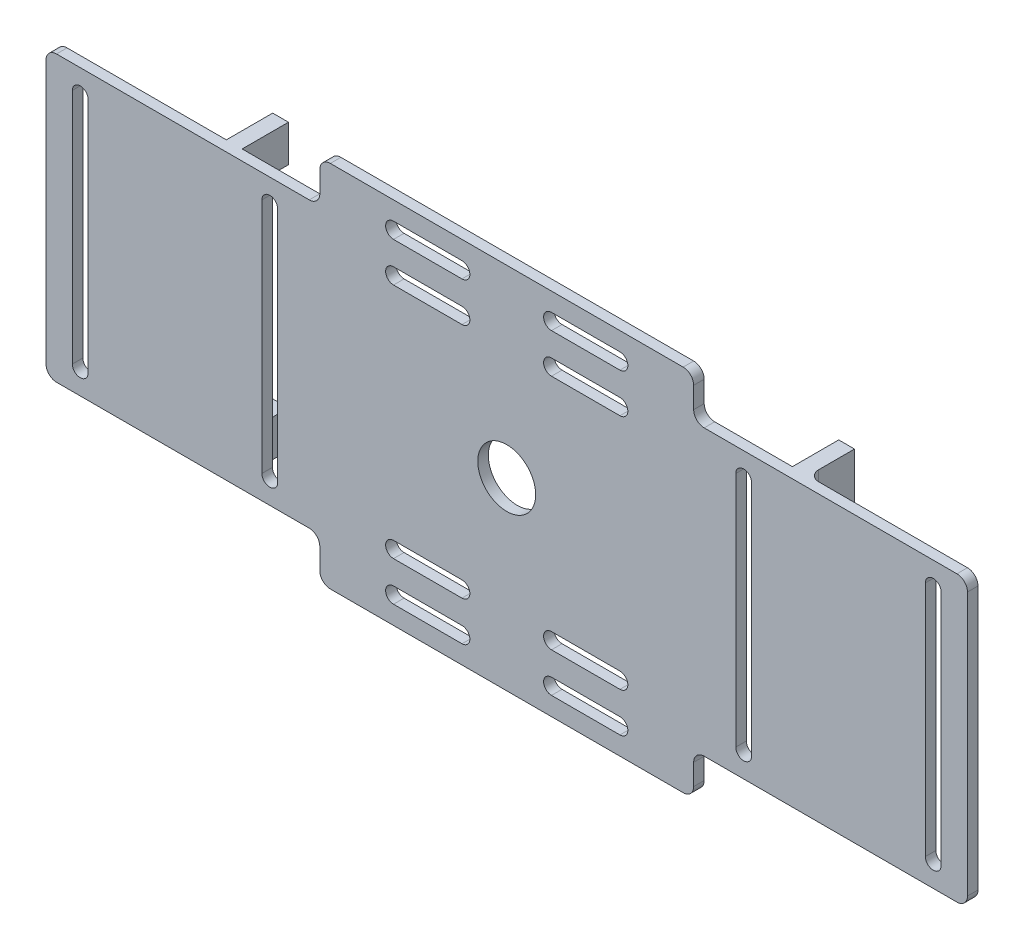
SolidWorks part; units mm, degrees
ref_plane "前基準面" through (0, 0, 0) normal (0, 0, 1) x (1, 0, 0)
ref_plane "上基準面" through (0, 0, 0) normal (0, 1, 0) x (1, 0, 0)
ref_plane "右基準面" through (0, 0, 0) normal (1, 0, 0) x (0, 0, -1)
sketch "草圖1" plane through (0, 0, 0) normal (0, 0, 1) x (1, 0, 0)
  line L0 (35.5, 33) -> (35.5, 29)
  line L1 (-33.5, 35) -> (33.5, 35)
  line L2 (-87.5, 25) -> (-87.5, -25)
  line L3 (-33.5, -35) -> (33.5, -35)
  line L4 (87.5, 25) -> (87.5, -25)
  line L5 (-85, 35) -> (85, -35) construction
  line L6 (-85, -35) -> (85, 35) construction
  line L7 (37.5, 27) -> (85.5, 27)
  line L8 (0, 72.342) -> (0, -45.5052) construction
  line L9 (-37.5, 27) -> (-85.5, 27)
  line L10 (124.9211, 0) -> (-91.026, 0) construction
  line L11 (-35.5, 33) -> (-35.5, 29)
  line L12 (37.5, -27) -> (85.5, -27)
  line L13 (35.5, -33) -> (35.5, -29)
  line L14 (-35.5, -33) -> (-35.5, -29)
  line L15 (-37.5, -27) -> (-85.5, -27)
  arc A0 (35.5, 33) -> (33.5, 35) centre (33.5, 33) ccw
  arc A1 (37.5, 27) -> (35.5, 29) centre (37.5, 29) cw
  arc A2 (87.5, 25) -> (85.5, 27) centre (85.5, 25) ccw
  arc A3 (-87.5, 25) -> (-85.5, 27) centre (-85.5, 25) cw
  arc A4 (-37.5, 27) -> (-35.5, 29) centre (-37.5, 29) ccw
  arc A5 (-35.5, 33) -> (-33.5, 35) centre (-33.5, 33) cw
  arc A6 (87.5, -25) -> (85.5, -27) centre (85.5, -25) cw
  arc A7 (37.5, -27) -> (35.5, -29) centre (37.5, -29) ccw
  arc A8 (35.5, -33) -> (33.5, -35) centre (33.5, -33) cw
  arc A9 (-35.5, -33) -> (-33.5, -35) centre (-33.5, -33) ccw
  arc A10 (-37.5, -27) -> (-35.5, -29) centre (-37.5, -29) cw
  arc A11 (-87.5, -25) -> (-85.5, -27) centre (-85.5, -25) ccw
  point P0 (0, 0)
  point P13 (35.5, 27)
  point P29 (-35.5, 27)
  point P39 (35.5, -27)
  point P49 (-35.5, -27)
  dimension "D1" = 2
  dimension "D2" = 2
  dimension "D3" = 2
  dimension "D4" = 175
  dimension "D5" = 70
  dimension "D6" = 52
  dimension "D7" = 8
extrude "填料-伸長1" add sketch "草圖1" along normal blind 2
sketch "草圖2" plane through (0, 0, 2) normal (0, 0, 1) x (1, 0, 0)
  line L0 (-1000, 0) -> (49000, 0) construction
  line L1 (45, -986.1952) -> (45, 49013.8048) construction
  line L2 (-81, -962.7943) -> (-81, 49037.2057) construction
  line L3 (45, -22.5) -> (45, 22.5) construction
  line L4 (43.5, -22.5) -> (43.5, 22.5)
  line L5 (46.5, -22.5) -> (46.5, 22.5)
  line L6 (-45, -1000) -> (-45, 49000) construction
  line L7 (-45, -22.5) -> (-45, 22.5) construction
  line L8 (-46.5, -22.5) -> (-46.5, 22.5)
  line L9 (-43.5, -22.5) -> (-43.5, 22.5)
  line L10 (0, -1000) -> (0, 49000) construction
  line L11 (-1005.6924, 30) -> (48994.3076, 30) construction
  line L12 (-1002.3566, -30) -> (48997.6434, -30) construction
  line L13 (21.5, 30) -> (8.5, 30) construction
  line L16 (21.5, 28.5) -> (8.5, 28.5)
  line L19 (81, -968.4295) -> (81, 49031.5705) construction
  line L20 (-81, -22.5) -> (-81, 22.5) construction
  line L21 (-82.5, -22.5) -> (-82.5, 22.5)
  line L22 (-79.5, -22.5) -> (-79.5, 22.5)
  line L23 (81, -22.5) -> (81, 22.5) construction
  line L24 (79.5, -22.5) -> (79.5, 22.5)
  line L25 (82.5, -22.5) -> (82.5, 22.5)
  line L26 (21.5, 31.5) -> (8.5, 31.5)
  line L27 (21.5, 22.5) -> (8.5, 22.5) construction
  line L28 (21.5, 21) -> (8.5, 21)
  line L29 (21.5, 24) -> (8.5, 24)
  line L30 (-21.5, 30) -> (-8.5, 30) construction
  line L31 (-21.5, 28.5) -> (-8.5, 28.5)
  line L32 (-21.5, 31.5) -> (-8.5, 31.5)
  line L33 (-21.5, 22.5) -> (-8.5, 22.5) construction
  line L34 (-21.5, 21) -> (-8.5, 21)
  line L35 (-21.5, 24) -> (-8.5, 24)
  line L36 (21.5, -30) -> (8.5, -30) construction
  line L37 (21.5, -28.5) -> (8.5, -28.5)
  line L38 (21.5, -31.5) -> (8.5, -31.5)
  line L39 (21.5, -22.5) -> (8.5, -22.5) construction
  line L40 (21.5, -21) -> (8.5, -21)
  line L41 (21.5, -24) -> (8.5, -24)
  line L42 (-21.5, -30) -> (-8.5, -30) construction
  line L43 (-21.5, -28.5) -> (-8.5, -28.5)
  line L44 (-21.5, -31.5) -> (-8.5, -31.5)
  line L45 (-21.5, -22.5) -> (-8.5, -22.5) construction
  line L46 (-21.5, -21) -> (-8.5, -21)
  line L47 (-21.5, -24) -> (-8.5, -24)
  arc A0 (43.5, -22.5) -> (46.5, -22.5) centre (45, -22.5) ccw
  arc A1 (46.5, 22.5) -> (43.5, 22.5) centre (45, 22.5) ccw
  arc A2 (-46.5, -22.5) -> (-43.5, -22.5) centre (-45, -22.5) ccw
  arc A3 (-43.5, 22.5) -> (-46.5, 22.5) centre (-45, 22.5) ccw
  arc A12 (-82.5, -22.5) -> (-79.5, -22.5) centre (-81, -22.5) ccw
  arc A13 (-79.5, 22.5) -> (-82.5, 22.5) centre (-81, 22.5) ccw
  arc A14 (79.5, -22.5) -> (82.5, -22.5) centre (81, -22.5) ccw
  arc A15 (82.5, 22.5) -> (79.5, 22.5) centre (81, 22.5) ccw
  circle A16 centre (0, 0) radius 5.5
  arc A17 (21.5, 28.5) -> (21.5, 31.5) centre (21.5, 30) ccw
  arc A18 (8.5, 31.5) -> (8.5, 28.5) centre (8.5, 30) ccw
  arc A19 (21.5, 21) -> (21.5, 24) centre (21.5, 22.5) ccw
  arc A20 (8.5, 24) -> (8.5, 21) centre (8.5, 22.5) ccw
  arc A21 (-21.5, 28.5) -> (-21.5, 31.5) centre (-21.5, 30) cw
  arc A22 (-8.5, 31.5) -> (-8.5, 28.5) centre (-8.5, 30) cw
  arc A23 (-21.5, 21) -> (-21.5, 24) centre (-21.5, 22.5) cw
  arc A24 (-8.5, 24) -> (-8.5, 21) centre (-8.5, 22.5) cw
  arc A25 (21.5, -28.5) -> (21.5, -31.5) centre (21.5, -30) cw
  arc A26 (8.5, -31.5) -> (8.5, -28.5) centre (8.5, -30) cw
  arc A27 (21.5, -21) -> (21.5, -24) centre (21.5, -22.5) cw
  arc A28 (8.5, -24) -> (8.5, -21) centre (8.5, -22.5) cw
  arc A29 (-21.5, -28.5) -> (-21.5, -31.5) centre (-21.5, -30) ccw
  arc A30 (-8.5, -31.5) -> (-8.5, -28.5) centre (-8.5, -30) ccw
  arc A31 (-21.5, -21) -> (-21.5, -24) centre (-21.5, -22.5) ccw
  arc A32 (-8.5, -24) -> (-8.5, -21) centre (-8.5, -22.5) ccw
  point P9 (45, 0)
  point P16 (-45, 0)
  point P31 (15, 30)
  point P39 (15, 22.5)
  point P47 (-81, 0)
  point P54 (81, 0)
  point P63 (-15, 30)
  point P70 (-15, 22.5)
  point P77 (15, -30)
  point P84 (15, -22.5)
  point P91 (-15, -30)
  point P98 (-15, -22.5)
  dimension "D10" = 1.5
  dimension "D20" = 11
  dimension "D12" = 8.5
  dimension "D2" = 45
  dimension "D3" = 3
  dimension "D4" = 90
  dimension "D5" = 45
  dimension "D6" = 3
  dimension "D7" = 45
  dimension "D8" = 60
  dimension "D9" = 30
  dimension "D11" = 13
  dimension "D13" = 2
  dimension "D14" = 162
  dimension "D15" = 81
  dimension "D16" = 3
  dimension "D17" = 45
  dimension "D18" = 45
  dimension "D19" = 3
extrude "除料-伸長1" cut sketch "草圖2" against normal through all
sketch "草圖5" plane through (0, 0, 2) normal (0, 0, 1) x (1, 0, 0)
  line L1 (-55.25, 27) -> (-52.25, 27)
  line L2 (-55.25, 27) -> (-55.25, -27)
  line L3 (-55.25, -27) -> (-52.25, -27)
  line L4 (-52.25, 27) -> (-52.25, -27)
  line L6 (0, 48.2539) -> (0, -45.9001) construction
  line L7 (52.25, 27) -> (52.25, -27)
  line L8 (55.25, -27) -> (52.25, -27)
  line L9 (55.25, 27) -> (55.25, -27)
  line L10 (55.25, 27) -> (52.25, 27)
  line L11 (-37.5, 27) -> (-85.5, 27) construction
  line L13 (-85.5, -27) -> (-37.5, -27) construction
  dimension "D1" = 3
  dimension "D2" = 52.25
extrude "填料-伸長2" add sketch "草圖5" against normal blind 10.8 contours L2 L3 L4 L1 | L7 L8 L9 L10
fillet "圓角1" radius 2 1 edges at (55.25, 0, 0)
sketch "草圖6" plane through (0, 0, -8.8) normal (0, 0, -1) x (-1, 0, 0)
  line L0 (-19.1896, 0) -> (94.9262, 0) construction
  line L1 (55.25, 27) -> (55.25, -27) construction
  line L2 (52.25, -20) -> (55.25, -20)
  line L3 (52.25, -20) -> (52.25, 20)
  line L4 (52.25, 20) -> (55.25, 20)
  line L5 (55.25, -20) -> (55.25, 20)
  line L6 (52.25, -20) -> (55.25, 20) construction
  line L7 (52.25, 20) -> (55.25, -20) construction
  line L8 (52.25, 27) -> (52.25, -27) construction
  point P2 (53.75, 0)
  dimension "D1" = 40
extrude "除料-伸長3" cut sketch "草圖6" against normal blind 6
fillet "圓角2" radius 2 2 edges at (-53.75, -20, -2.8) (-53.75, 20, -2.8)
